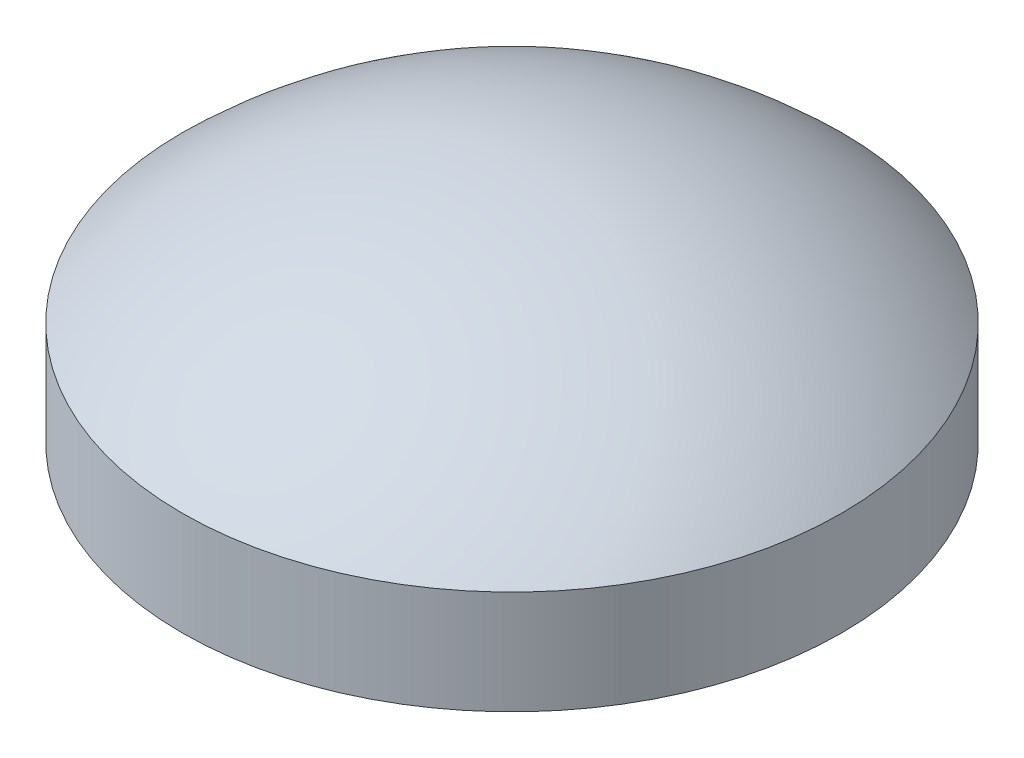
SolidWorks part; units mm, degrees
material "ABS PC"
ref_plane "Front Plane" through (0, 0, 0) normal (0, 0, 1) x (1, 0, 0)
ref_plane "Top Plane" through (0, 0, 0) normal (0, 1, 0) x (1, 0, 0)
ref_plane "Right Plane" through (0, 0, 0) normal (1, 0, 0) x (0, 0, -1)
sketch "Sketch3" plane through (0, 0, 0) normal (0, 1, 0) x (-1, 0, 0)
  circle A0 centre (0, 0) radius 39.75
  dimension "D1" = 79.5
extrude "Boss-Extrude2" add sketch "Sketch3" along normal blind 12.5
dome "Dome1" faces to dome 1 distance 16 reverse direction no elliptical dome no face at (0, 12.5, 39.75) parameters "D1"=16
